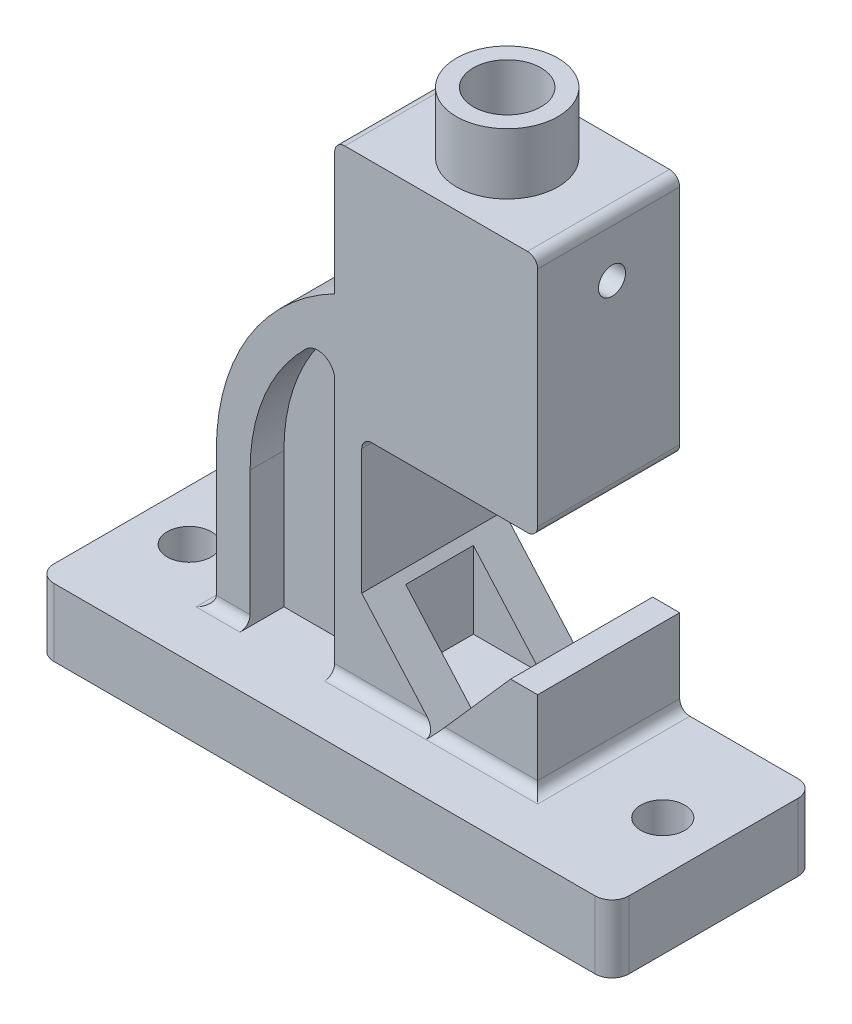
SolidWorks part; units mm, degrees
ref_plane "Front Plane" through (0, 0, 0) normal (0, 0, 1) x (1, 0, 0)
ref_plane "Top Plane" through (0, 0, 0) normal (0, 1, 0) x (1, 0, 0)
ref_plane "Right Plane" through (0, 0, 0) normal (1, 0, 0) x (0, 0, -1)
sketch "Sketch1" plane through (0, 0, 0) normal (0, 0, 1) x (1, 0, 0)
  line L0 (0, 0) -> (-84704.8391, 0) construction
  line L1 (0, 0) -> (0, 84704.8391) construction
  line L2 (0, 0) -> (170, 0)
  line L3 (170, 0) -> (170, 20)
  line L4 (170, 20) -> (130, 20)
  line L5 (130, 20) -> (130, 45)
  line L6 (130, 45) -> (122, 45)
  line L7 (122, 45) -> (100, 20)
  line L8 (100, 20) -> (78, 45)
  line L9 (78, 45) -> (78, 85)
  line L10 (78, 85) -> (130, 85)
  line L11 (130, 85) -> (130, 157)
  line L12 (130, 157) -> (115, 157)
  line L13 (115, 157) -> (115, 175)
  line L14 (115, 175) -> (85, 175)
  line L15 (85, 175) -> (85, 157)
  line L16 (85, 157) -> (70, 157)
  line L17 (70, 157) -> (70, 117.6628)
  line L18 (35, 60) -> (35, 20)
  line L19 (70, 20) -> (70, 95.7071)
  line L20 (45, 20) -> (45, 60)
  line L21 (0, 0) -> (0, 20)
  line L22 (130, 20) -> (0, 20)
  arc A0 (70, 117.6628) -> (35, 60) centre (100, 60) ccw
  arc A1 (45, 60) -> (61.5, 99.2779) centre (100, 60) cw
  arc A2 (70, 95.7071) -> (61.5, 99.2779) centre (65, 95.7071) ccw
  dimension "D9" = 65
  dimension "D10" = 55
  dimension "D8" = 5
  dimension "D1" = 170
  dimension "D2" = 20
  dimension "D3" = 25
  dimension "D4" = 60
  dimension "D5" = 44
  dimension "D6" = 72
  dimension "D7" = 40
  dimension "D12" = 60
  dimension "D14" = 70
  dimension "D15" = 30
  dimension "D16" = 25
  dimension "D18" = 18
extrude "Boss-Extrude1" add sketch "Sketch1" along normal blind 60 contours L4 L22 L21 L2 L3 region at (85, 10, 0)
extrude "Boss-Extrude2" add sketch "Sketch1<3>" along normal blind 42 contours L20 A1 L19 L22 L8 L9 L10 L11 L12 L13 L14 L15 L16 L17 A0 L18 | L22 L5 L6 L7 region at (89.0237, 107.5953, 0) region at (119.4386, 30.0877, 0)
sketch "Sketch1<3>" plane through (0, 0, 0) normal (0, 0, 1) x (1, 0, 0) same geometry as "Sketch1"
ref_plane "Plane1" through (0, 0, 10) normal (0, 0, -1) x (-1, 0, 0)
sketch "Sketch3" plane through (115, 0, 0) normal (1, 0, 0) x (0, 0, -1)
  line L0 (-42, 157) -> (7.234, 157)
  line L1 (7.234, 157) -> (7.234, 179.6275)
  line L2 (7.234, 179.6275) -> (-54.6344, 179.6275)
  line L3 (-54.6344, 179.6275) -> (-54.6344, 157)
  line L4 (-54.6344, 157) -> (-42, 157)
extrude "Cut-Extrude1" cut sketch "Sketch3" against normal blind 42
sketch "Sketch4" plane through (0, 157, 0) normal (0, 1, 0) x (1, 0, 0)
  line L0 (130, 0) -> (70, 0) construction
  line L1 (130, -42) -> (130, 0) construction
  circle A0 centre (100, -21) radius 15
  circle A1 centre (100, -21) radius 10
  dimension "D1" = 30
  dimension "D2" = 20
  dimension "D3" = 21
  dimension "D4" = 30
extrude "Boss-Extrude4" add sketch "Sketch4" along normal blind 18
extrude "Cut-Extrude2" cut sketch "Sketch4<2>" against normal blind 10 contours A1 region at (100, 157, 21)
sketch "Sketch4<2>" plane through (0, 157, 0) normal (0, 1, 0) x (1, 0, 0) same geometry as "Sketch4"
sketch "Sketch5" plane through (0, 147, 0) normal (0, 1, 0) x (1, 0, 0)
  line L1 (80, -31) -> (120, -31)
  line L2 (80, -31) -> (80, -11)
  line L3 (80, -11) -> (120, -11)
  line L4 (120, -31) -> (120, -11)
  line L5 (80, -31) -> (120, -11) construction
  line L6 (80, -11) -> (120, -31) construction
  point P0 (100, -21)
  dimension "D1" = 40
  dimension "D2" = 20
extrude "Cut-Extrude3" cut sketch "Sketch5" against normal up to surface (127 mm away) up to face at (76.9231, 20, 25.3846)
sketch "Sketch6" plane through (0, 20, 0) normal (0, 1, 0) x (1, 0, 0)
  line L0 (0, -60) -> (0, 0) construction
  line L1 (170, -60) -> (170, 0) construction
  line L2 (35, 0) -> (0, 0) construction
  line L3 (170, 0) -> (130, 0) construction
  circle A0 centre (15, -30) radius 6.5
  circle A1 centre (155, -30) radius 6.5
  point P8 (0, 0)
  dimension "D1" = 13
  dimension "D2" = 15
  dimension "D3" = 15
  dimension "D4" = 30
  dimension "D5" = 30
extrude "Cut-Extrude4" cut sketch "Sketch6" against normal blind 183
sketch "Sketch7" plane through (130, 0, 0) normal (1, 0, 0) x (0, 0, -1)
  line L0 (-42, 157) -> (0, 157) construction
  line L1 (0, 85) -> (0, 157) construction
  circle A0 centre (-20, 140) radius 4
  dimension "D1" = 8
  dimension "D2" = 17
  dimension "D3" = 20
extrude "Cut-Extrude5" cut sketch "Sketch7" against normal blind 245
fillet "Fillet1" radius 3 9 edges at (115, 20, 42) (78, 85, 21) (70, 157, 21) (130, 157, 21) (130, 85, 21) (130, 20, 21) (85, 20, 42) (35, 20, 21) (40, 20, 42)
fillet "Fillet2" radius 5 4 edges at (170, 10, 0) (0, 10, 0) (0, 10, 60) (170, 10, 60)
sketch "Sketch8" plane through (0, 0, 10) normal (0, 0, -1) x (-1, 0, 0)
  line L0 (-130, 20) -> (-130, 45) construction
  line L1 (-130, 45) -> (-122, 45) construction
  line L2 (-122, 45) -> (-100, 20) construction
  line L3 (-100, 20) -> (-78, 45) construction
  line L4 (-78, 45) -> (-78, 85) construction
  line L5 (-78, 85) -> (-130, 85) construction
  line L6 (-130, 85) -> (-130, 157) construction
  line L7 (-130, 157) -> (-115, 157) construction
  line L8 (-115, 157) -> (-115, 175) construction
  line L9 (-115, 175) -> (-85, 175) construction
  line L10 (-85, 175) -> (-85, 157) construction
  line L11 (-85, 157) -> (-70, 157) construction
  line L12 (-70, 157) -> (-70, 117.6628) construction
  line L13 (-35, 60) -> (-35, 20) construction
  line L14 (-45, 20) -> (-45, 60) construction
  line L15 (-70, 20) -> (-70, 95.7071) construction
  line L16 (-170, 20) -> (-130, 20) construction
  line L17 (-170, 0) -> (-170, 20) construction
  line L18 (0, 0) -> (-170, 0) construction
  line L19 (0, 0) -> (0, 20) construction
  line L20 (-130, 20) -> (0, 20) construction
  line L21 (-130, 20) -> (-130, 45)
  line L22 (-130, 45) -> (-122, 45)
  line L23 (-122, 45) -> (-100, 20)
  line L24 (-100, 20) -> (-78, 45)
  line L25 (-78, 45) -> (-78, 85)
  line L26 (-78, 85) -> (-130, 85)
  line L27 (-130, 85) -> (-130, 157)
  line L28 (-130, 157) -> (-115, 157)
  line L29 (-115, 157) -> (-115, 175)
  line L30 (-115, 175) -> (-85, 175)
  line L31 (-85, 175) -> (-85, 157)
  line L32 (-85, 157) -> (-70, 157)
  line L33 (-70, 157) -> (-70, 117.6628)
  line L34 (-35, 60) -> (-35, 20)
  line L35 (-45, 20) -> (-45, 60)
  line L36 (-70, 20) -> (-70, 95.7071)
  line L37 (-170, 20) -> (-130, 20)
  line L38 (-170, 0) -> (-170, 20)
  line L39 (0, 0) -> (-170, 0)
  line L40 (0, 0) -> (0, 20)
  line L41 (-130, 20) -> (-100, 20)
  line L42 (-70, 20) -> (-45, 20)
  line L43 (-70, 20) -> (-45, 20)
  line L44 (-35, 20) -> (0, 20)
  arc A0 (-35, 60) -> (-70, 117.6628) centre (-100, 60) ccw construction
  arc A1 (-45, 60) -> (-61.5, 99.2779) centre (-100, 60) ccw construction
  arc A2 (-61.5, 99.2779) -> (-70, 95.7071) centre (-65, 95.7071) ccw construction
  arc A3 (-35, 60) -> (-70, 117.6628) centre (-100, 60) ccw
  arc A4 (-45, 60) -> (-61.5, 99.2779) centre (-100, 60) ccw
  arc A5 (-61.5, 99.2779) -> (-70, 95.7071) centre (-65, 95.7071) ccw
extrude "Boss-Extrude6" add sketch "Sketch8" against normal blind 22 contours A4 A5 L36 L42 L35 region at (58.386, 56.3637, 10)
